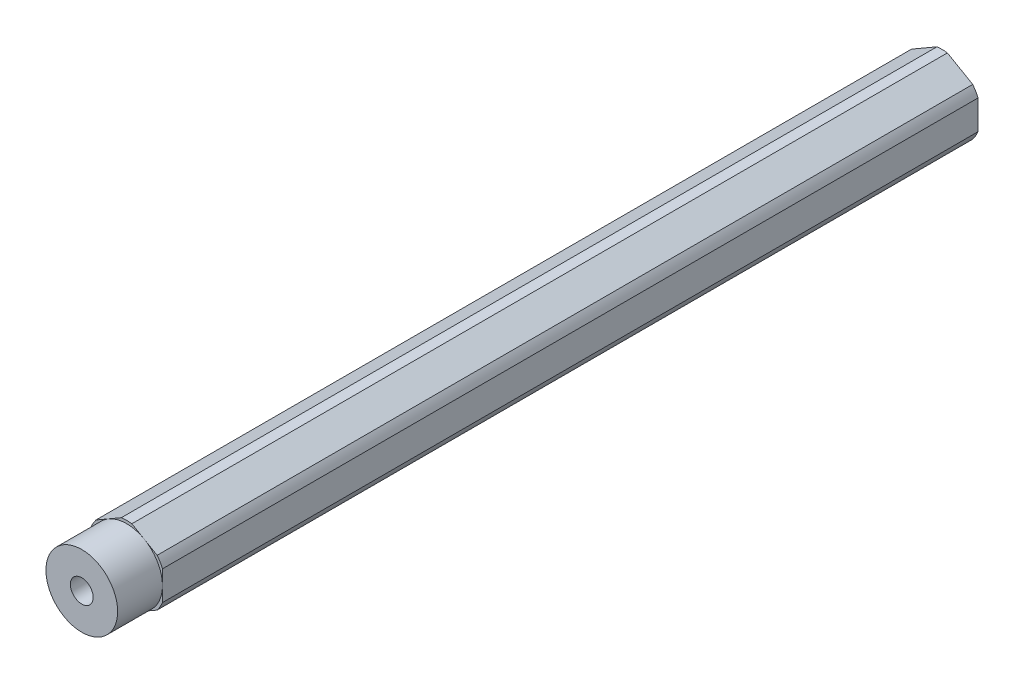
SolidWorks part; units mm, degrees
ref_plane "Front Plane" through (0, 0, 0) normal (0, 0, 1) x (1, 0, 0)
ref_plane "Top Plane" through (0, 0, 0) normal (0, 1, 0) x (1, 0, 0)
ref_plane "Right Plane" through (0, 0, 0) normal (1, 0, 0) x (0, 0, -1)
sketch "Sketch1" plane through (0, 0, 0) normal (0, 0, 1) x (1, 0, 0)
  line L1 (0, 7.3323) -> (-6.35, 3.6662)
  line L2 (-6.35, 3.6662) -> (-6.35, -3.6662)
  line L3 (-6.35, -3.6662) -> (0, -7.3323)
  line L4 (0, -7.3323) -> (6.35, -3.6662)
  line L5 (6.35, -3.6662) -> (6.35, 3.6662)
  line L6 (6.35, 3.6662) -> (0, 7.3323)
  circle A0 centre (0, 0) radius 6.35 construction
  circle A1 centre (0, 0) radius 6.858
  circle A2 centre (0, 0) radius 2.0193 construction
  dimension "D1" = 12.7
  dimension "D2" = 13.716
  dimension "D3" = 4.0386
extrude "Boss-Extrude1" add sketch "Sketch1" along normal mid plane 144.4625 contours L5 A1 L6 L1 L2 L3 L4 region at (0, 0, 0)
sketch "Sketch2" plane through (0, 0, 72.2313) normal (0, 0, 1) x (1, 0, 0)
  circle A0 centre (0, 0) radius 6.35
  circle A1 centre (0, 0) radius 2.0193
  point P4 (0, 0)
  dimension "D1" = 12.7
  dimension "D2" = 4.0386
extrude "Boss-Extrude2" add sketch "Sketch2" along normal blind 7.9375
hole_wizard "#10-32 Tapped Hole1" positions "Sketch3" profile "Sketch4" tap size "#10-32" standard "ANSI Inch" end condition through all
sketch "Sketch3" plane through (0, 0, -72.2313) normal (0, 0, -1) x (-1, 0, 0)
  point P0 (0, 0)
sketch "Sketch4" plane through (0, 0, -72.2313) normal (1, 0, 0) x (0, 1, 0)
  line L0 (0, 0) -> (0, 152.4)
  line L1 (0, 152.4) -> (2.0193, 152.4)
  line L2 (2.0193, 152.4) -> (2.0193, 0)
  line L5 (2.0193, 0) -> (0, 0)
  line L11 (0, -6.35) -> (0, 107.95) construction
  dimension "Thru Tap Drill Dia." = 4.0386
  dimension "Thru Tap Drill Depth" = 152.4
cosmetic thread "Hole Thread1" parameters "D2"=4.826
